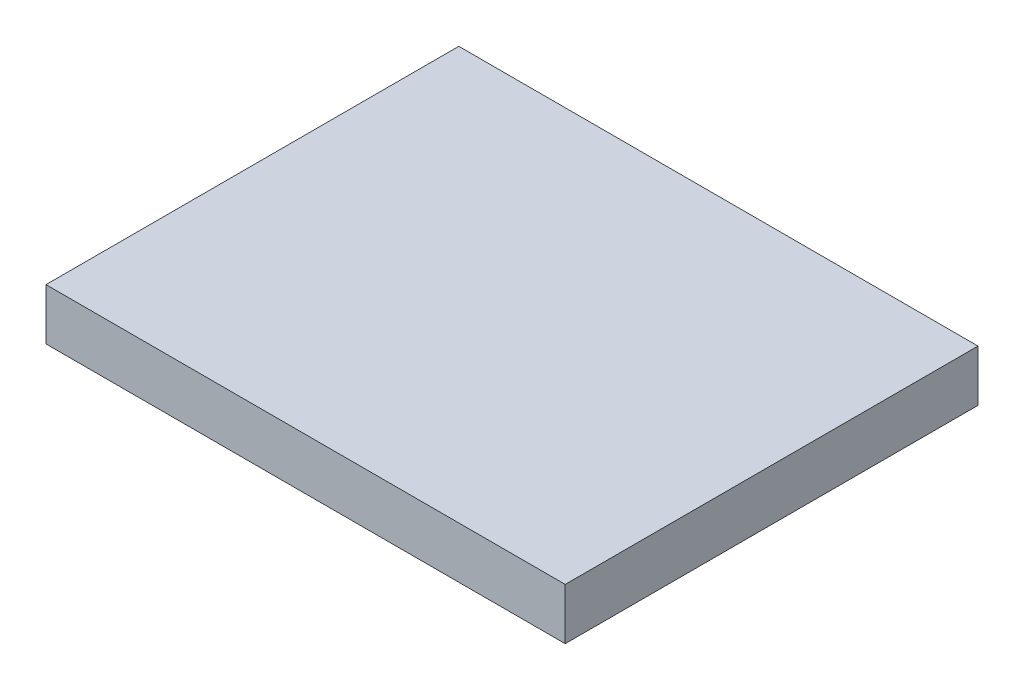
SolidWorks part; units mm, degrees
ref_plane "Front Plane" through (0, 0, 0) normal (0, 0, 1) x (1, 0, 0)
ref_plane "Top Plane" through (0, 0, 0) normal (0, 1, 0) x (1, 0, 0)
ref_plane "Right Plane" through (0, 0, 0) normal (1, 0, 0) x (0, 0, -1)
sketch "Sketch1" plane through (0, 0, 0) normal (0, 1, 0) x (1, 0, 0)
  line L1 (0, 0) -> (283, 0)
  line L2 (0, 0) -> (0, 225)
  line L3 (0, 225) -> (283, 225)
  line L4 (283, 0) -> (283, 225)
  dimension "D1" = 225
  dimension "D2" = 283
extrude "Boss-Extrude1" add sketch "Sketch1" along normal blind 28
sketch "Sketch2" plane through (0, 0, 0) normal (0, -1, 0) x (1, 0, 0)
  line L0 (0, 0) -> (283, 0) construction
  line L1 (283, -225) -> (0, -225) construction
  line L2 (0, -225) -> (0, 0) construction
  line L3 (283, 0) -> (283, -225) construction
  circle A0 centre (25, -25) radius 10
  circle A1 centre (25, -200) radius 10
  circle A2 centre (258, -200) radius 10
  circle A3 centre (258, -25) radius 10
  dimension "D1" = 20
  dimension "D10" = 20
  dimension "D11" = 20
  dimension "D12" = 20
  dimension "D2" = 25
  dimension "D3" = 25
  dimension "D4" = 25
  dimension "D5" = 25
  dimension "D6" = 25
  dimension "D7" = 25
  dimension "D8" = 25
  dimension "D9" = 25
extrude "Boss-Extrude2" add sketch "Sketch2" along normal blind 6.5
equation "\"Length\"= 283mm"
equation "\"Width\"= 225mm"
equation "\"WallThickness\"= 12.5mm"
equation "\"D1@Sketch1\"=\"Width\""
equation "\"D2@Sketch1\"=\"Length\""
equation "\"UpperWaterJacketThickness\"= 28mm"
equation "\"D1@Boss-Extrude1\"=\"UpperWaterJacketThickness\""
equation "\"UpperWaterJacketPegDiameter\"=20"
equation "\"D1@Sketch2\"=\"UpperWaterJacketPegDiameter\""
equation "\"UpperWaterJacketPegDistance\"=2.5"
equation "\"D2@Sketch2\"=\"WallThickness\"+\"UpperWaterJacketPegDiameter\"/2+\"UpperWaterJacketPegDistance\""
equation "\"D3@Sketch2\"=\"WallThickness\"+\"UpperWaterJacketPegDiameter\"/2+\"UpperWaterJacketPegDistance\""
equation "\"D4@Sketch2\"=\"WallThickness\"+\"UpperWaterJacketPegDiameter\"/2+\"UpperWaterJacketPegDistance\""
equation "\"D5@Sketch2\"=\"WallThickness\"+\"UpperWaterJacketPegDiameter\"/2+\"UpperWaterJacketPegDistance\""
equation "\"D6@Sketch2\"=\"WallThickness\"+\"UpperWaterJacketPegDiameter\"/2+\"UpperWaterJacketPegDistance\""
equation "\"D7@Sketch2\"=\"WallThickness\"+\"UpperWaterJacketPegDiameter\"/2+\"UpperWaterJacketPegDistance\""
equation "\"D8@Sketch2\"=\"WallThickness\"+\"UpperWaterJacketPegDiameter\"/2+\"UpperWaterJacketPegDistance\""
equation "\"D9@Sketch2\"=\"WallThickness\"+\"UpperWaterJacketPegDiameter\"/2+\"UpperWaterJacketPegDistance\""
equation "\"D10@Sketch2\"=\"UpperWaterJacketPegDiameter\""
equation "\"D11@Sketch2\"=\"UpperWaterJacketPegDiameter\""
equation "\"D12@Sketch2\"=\"UpperWaterJacketPegDiameter\""
equation "\"UpperWaterJacketPegHeight\"=6.5"
equation "\"D1@Boss-Extrude2\"=\"UpperWaterJacketPegHeight\""
equation "\"SpacerHeight\"= 80.2mm"
equation "\"SpacerCornerWidth\"= 10mm"
equation "\"SpacerCornerHeight\"= 60.16mm"
equation "\"SpacerPegDiameter\"= 10mm"
equation "\"SpacerPegHeight\"= 10mm"
equation "\"TubingShort\"= 110mm"
equation "\"TubingLong\"= 175mm"
equation "\"PlateLength\"= 252mm"
equation "\"PlateWidth\"= 190mm"
equation "\"PlateHoleDiameter\"= 5.9mm"
equation "\"PlateHoleBottom\"= 2mm"
equation "\"PlateHoleSide\"= 1.55mm"
equation "\"PlateHoleSpacing\"= 3.1mm"
equation "\"PlateThickness\"= 1.55mm"
equation "\"ReservoirBottom\"= 12.5mm"
equation "\"ReservoirSupportWidth\"= 12mm"
equation "\"ReservoirSupportHeight\"= 15.1mm"
equation "\"ReservoirSupportPlacementHeight\"= 50mm"
equation "\"ReservoirHoleDiameter\"= 12.7mm"
equation "\"ReservoirHoleRight\"= 25mm"
equation "\"ReservoirHoleTop\"= \"ReservoirSupportPlacementHeight\""
equation "\"ReservoirHeight\"= 90mm"
equation "\"ReservoirPortBottom\"= 4mm"
equation "\"ReservoirPortTop\"= 10mm"
equation "\"ReservoirPortWidth\"= 101mm"
equation "\"CustomSpacerWallThickness\"= 0.375in"
equation "\"CustomSpacerHeight\"= 5in"
equation "\"CustomSpacerRodHoleHeight\"= .75in"
equation "\"CustomSpacerRodHoleDiameter\"= .3125in"
equation "\"ScrewBlockSide\"= 12mm"
equation "\"ScrewBlockUpperHeight\"= 16mm"
equation "\"ScrewBlockLowerHeight\"= 16mm"
equation "\"InternalLength\"= \"Length\" - ( 2 * \"WallThickness\" )"
equation "\"InternalWidth\"= \"Width\" - ( 2 * \"WallThickness\" )"
